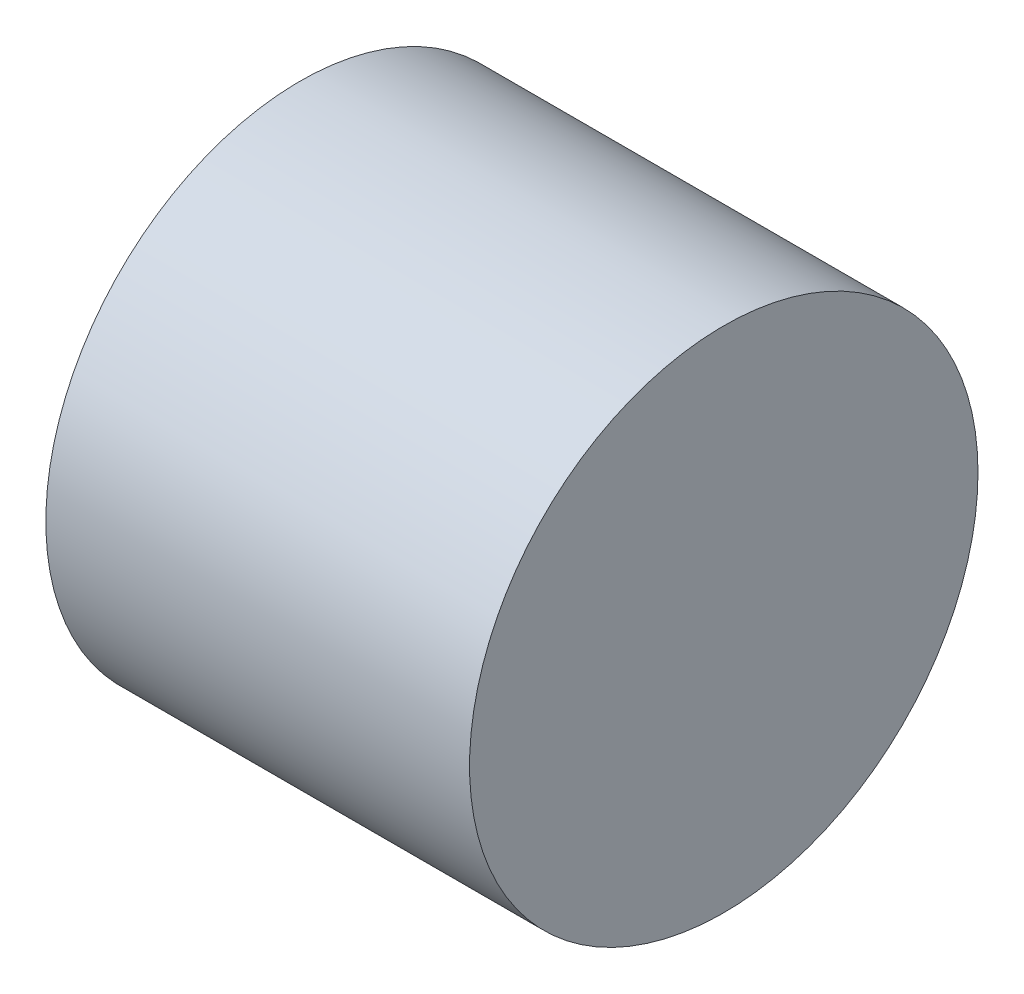
SolidWorks part; units mm, degrees
ref_plane "Front Plane" through (0, 0, 0) normal (0, 0, 1) x (1, 0, 0)
ref_plane "Top Plane" through (0, 0, 0) normal (0, 1, 0) x (1, 0, 0)
ref_plane "Right Plane" through (0, 0, 0) normal (1, 0, 0) x (0, 0, -1)
sketch "Sketch1" plane through (0, 0, 0) normal (1, 0, 0) x (0, 0, -1)
  circle A0 centre (0, 0) radius 150
  dimension "D1" = 300
extrude "Boss-Extrude1" add sketch "Sketch1" along normal blind 250
ref_axis "Axis1" through (250, 0, 0) along (-1, 0, 0)
